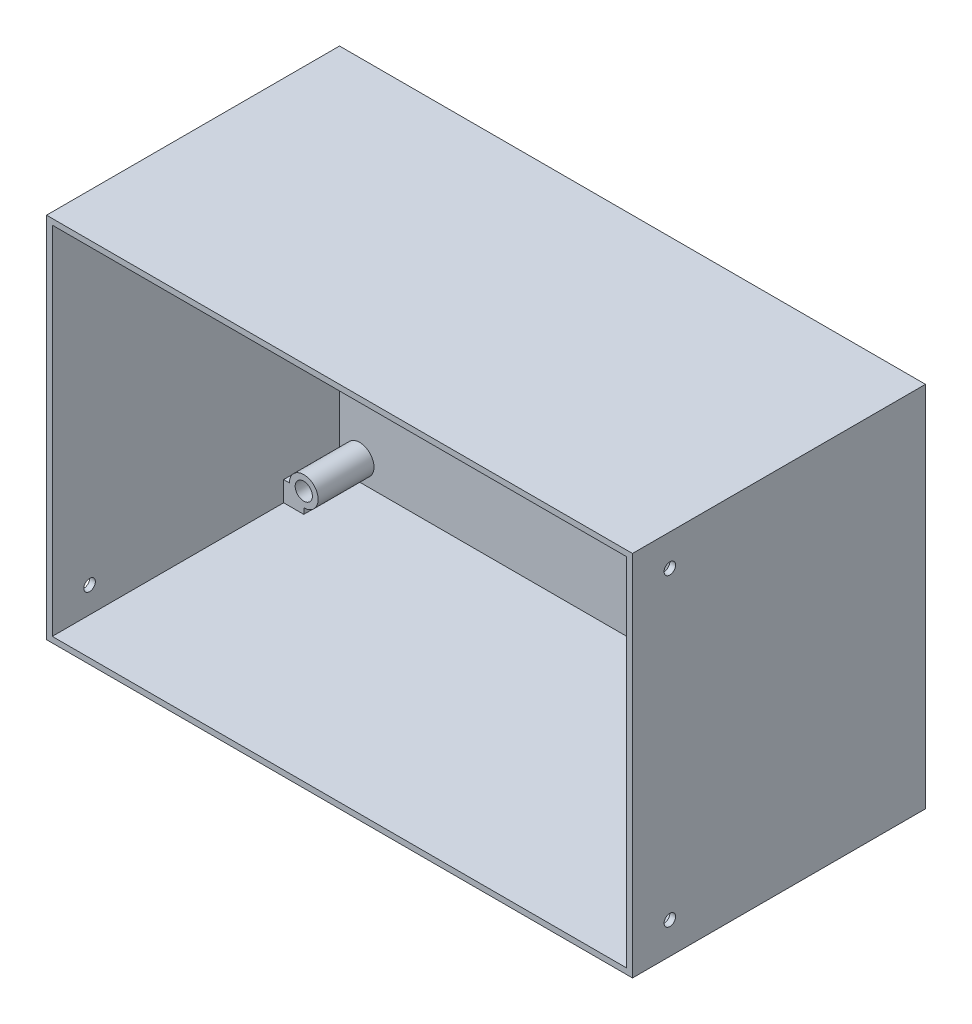
SolidWorks part; units mm, degrees
ref_plane "Спереди" through (0, 0, 0) normal (0, 0, 1) x (1, 0, 0)
ref_plane "Сверху" through (0, 0, 0) normal (0, 1, 0) x (1, 0, 0)
ref_plane "Справа" through (0, 0, 0) normal (1, 0, 0) x (0, 0, -1)
sketch "Эскиз1" plane through (0, 0, 0) normal (0, 0, 1) x (1, 0, 0)
  line L0 (2, 66) -> (2, 2)
  line L1 (2, 2) -> (104, 2)
  line L2 (104, 2) -> (104, 66)
  line L3 (104, 66) -> (2, 66)
  line L13 (3, 65) -> (103, 65)
  line L14 (103, 65) -> (103, 3)
  line L15 (103, 3) -> (3, 3)
  line L16 (3, 3) -> (3, 65)
  line L17 (102, 61.5) -> (103, 61.5)
  line L18 (99.5, 64) -> (99.5, 65)
  line L19 (6.5, 64) -> (6.5, 65)
  line L20 (4, 61.5) -> (3, 61.5)
  line L21 (4, 6.5) -> (3, 6.5)
  line L22 (6.5, 4) -> (6.5, 3)
  line L23 (99.5, 4) -> (99.5, 3)
  line L24 (102, 6.5) -> (103, 6.5)
  line L33 (15, 46.9) -> (91, 46.9)
  line L34 (91, 21.1) -> (15, 21.1)
  line L35 (15, 46.9) -> (15, 21.1)
  line L36 (91, 46.9) -> (91, 21.1)
  circle A0 centre (6.5, 61.5) radius 1.5
  arc A1 (6.5, 64) -> (4, 61.5) centre (6.5, 61.5) cw
  circle A2 centre (99.5, 61.5) radius 1.5
  arc A3 (99.5, 64) -> (102, 61.5) centre (99.5, 61.5) ccw
  circle A4 centre (99.5, 6.5) radius 1.5
  arc A5 (99.5, 4) -> (102, 6.5) centre (99.5, 6.5) cw
  circle A6 centre (6.5, 6.5) radius 1.5
  arc A7 (4, 6.5) -> (6.5, 4) centre (6.5, 6.5) cw
  dimension "D8" = 1
  dimension "D10" = 1
  dimension "D9" = 1
  dimension "D1" = 64
  dimension "D2" = 102
  dimension "D7" = 1
extrude "Бобышка-Вытянуть1" add sketch "Эскиз1" along normal blind 50 contours L0 L1 L2 L14 L15 L16 | L0 L16 L13 L14 L2 L3 region at (53, 65.8796, 0)
extrude "Бобышка-Вытянуть2" add sketch "Эскиз1<3>" along normal blind 9.72 contours A1 L19 L13 L16 L20 A0 | L18 A3 L17 L14 L13 A2 | A5 L23 L15 L14 L24 A4 | A7 L21 L16 L15 L22 A6 region at (4.75, 64.9151, 0) region at (101.25, 64.9151, 0) region at (3.5, 6.4151, 0) region at (102.9151, 4.75, 0)
sketch "Эскиз1<3>" plane through (0, 0, 0) normal (0, 0, 1) x (1, 0, 0) same geometry as "Эскиз1"
sketch "Эскиз4" plane through (0, 66, 0) normal (0, 1, 0) x (1, 0, 0)
  line L0 (2, 0) -> (2, 1)
  line L1 (2, 0) -> (104, 0)
  line L2 (104, 0) -> (104, 1)
  line L3 (2, 1) -> (104, 1)
extrude "Бобышка-Вытянуть3" add sketch "Эскиз4" against normal blind 64
extrude "Вырез-Вытянуть1" cut sketch "Эскиз1<5>" against normal blind 1 contours L36 L33 L35 L34 region at (53, 34, 0)
sketch "Эскиз1<5>" plane through (0, 0, 0) normal (0, 0, 1) x (1, 0, 0) same geometry as "Эскиз1"
sketch "Эскиз5" plane through (103, 0, 0) normal (-1, 0, 0) x (0, 0, 1)
  circle A0 centre (43.5, 7.5) radius 1
  circle A1 centre (43.5, 60.5) radius 1
extrude "Вырез-Вытянуть2" cut sketch "Эскиз5" along normal blind 102 and the other way blind 1
